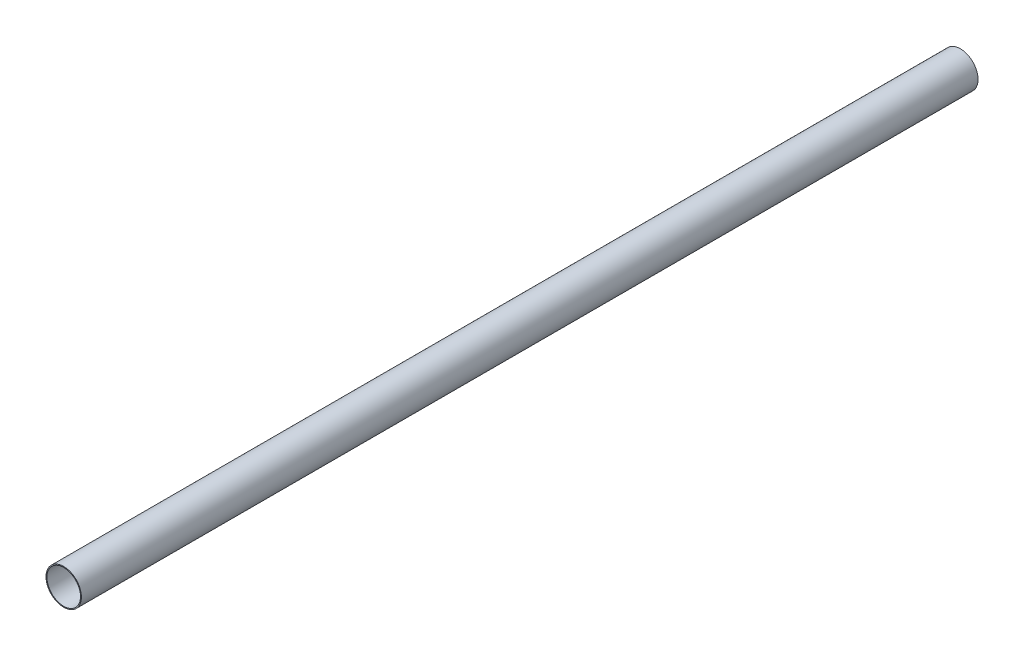
SolidWorks part; units mm, degrees
ref_plane "Ebene vorne" through (0, 0, 0) normal (0, 0, 1) x (1, 0, 0)
ref_plane "Ebene oben" through (0, 0, 0) normal (0, 1, 0) x (1, 0, 0)
ref_plane "Ebene rechts" through (0, 0, 0) normal (1, 0, 0) x (0, 0, -1)
sketch "Skizze1" plane through (0, 0, 0) normal (0, 0, 1) x (1, 0, 0)
  circle A3 centre (0, 0) radius 37.5
  dimension "D1" = 75
extrude "Aufsatz-Linear austragen2" add sketch "Skizze1" along normal blind 1900 contours A3
shell "Wandung2" thickness 1.9 removed face at (37.5, 0, 0) removed face at (37.5, 0, 1900)
ref_axis "Achse1" through (0, 0, 2670.4866) along (0, 0, -1)
